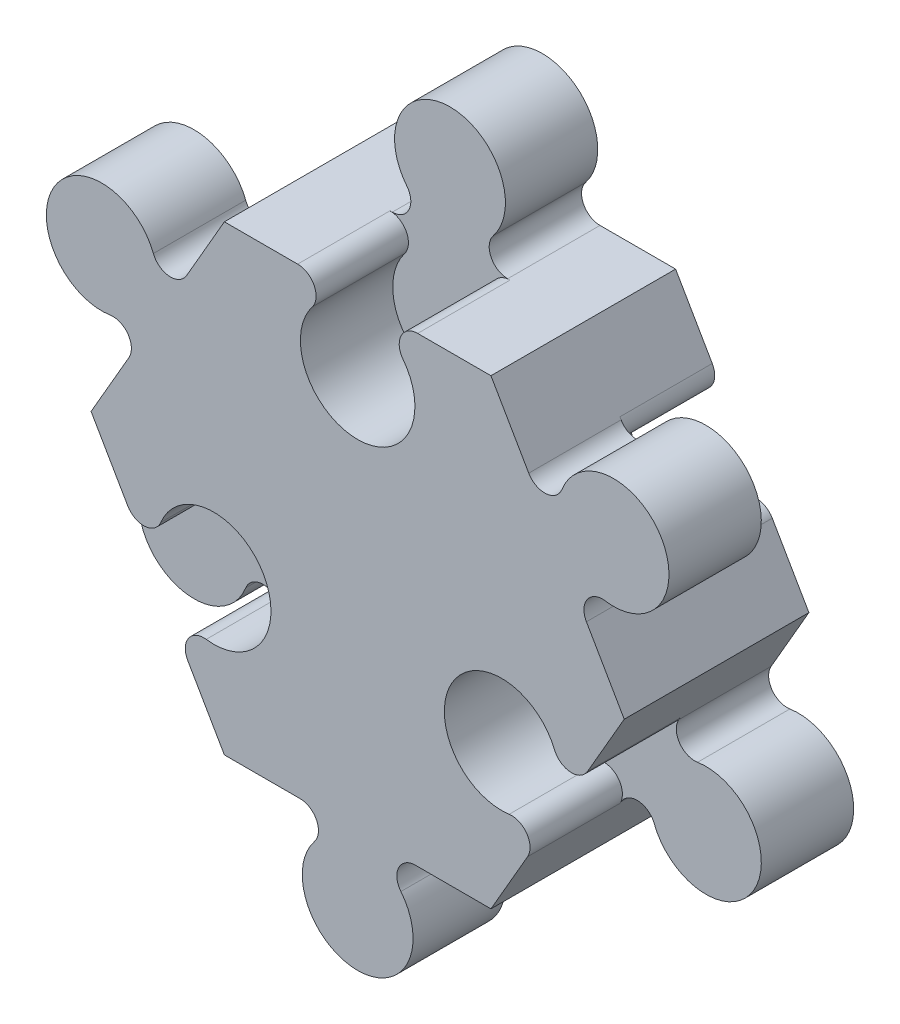
SolidWorks part; units mm, degrees
ref_plane "前视基准面" through (0, 0, 0) normal (0, 0, 1) x (1, 0, 0)
ref_plane "上视基准面" through (0, 0, 0) normal (0, 1, 0) x (1, 0, 0)
ref_plane "右视基准面" through (0, 0, 0) normal (1, 0, 0) x (0, 0, -1)
sketch "草图1" plane through (0, 0, 0) normal (0, 0, 1) x (1, 0, 0)
  line L1 (14.4338, 0) -> (7.2169, 12.5)
  line L2 (7.2169, 12.5) -> (-7.2169, 12.5)
  line L3 (-7.2169, 12.5) -> (-14.4338, 0)
  line L4 (-14.4338, 0) -> (-7.2169, -12.5)
  line L5 (-7.2169, -12.5) -> (7.2169, -12.5)
  line L6 (7.2169, -12.5) -> (14.4338, 0)
  circle A0 centre (0, 0) radius 12.5 construction
  point P1 (0, 0)
  dimension "D1" = 25
extrude "凸台-拉伸1" add sketch "草图1" along normal blind 10
sketch "草图2" plane through (0, 0, 0) normal (0, 0, -1) x (-1, 0, 0)
  line L2 (-7.2169, 12.5) -> (7.2169, 12.5) construction
  line L3 (-3.1225, 12.5) -> (3.1225, 12.5)
  line L4 (0, 19.7238) -> (0, 10.5872) construction
  arc A0 (2.3419, 14.125) -> (-2.3419, 14.125) centre (0, 16) ccw
  arc A1 (2.3419, 14.125) -> (3.1225, 12.5) centre (3.1225, 13.5) ccw
  arc A2 (-2.3419, 14.125) -> (-3.1225, 12.5) centre (-3.1225, 13.5) cw
  point P9 (0, 16.1627)
  dimension "D1" = 6
  dimension "D2" = 2
  dimension "D3" = 3.5
extrude "凸台-拉伸2" add sketch "草图2" against normal blind 5
sketch "草图3" plane through (0, 0, 0) normal (0, 0, -1) x (-1, 0, 0)
  line L0 (-3.1225, -12.5) -> (3.1225, -12.5) construction
  line L1 (7.2169, -12.5) -> (-7.2169, -12.5) construction
  line L2 (-3.2496, -12.5) -> (0, -12.5)
  line L3 (0, 1.3937) -> (0, -16.0678) construction
  line L4 (3.2496, -12.5) -> (-3.2496, -12.5)
  arc A6 (2.3419, -10.875) -> (-2.3419, -10.875) centre (0, -9) ccw construction
  arc A7 (2.3419, -10.875) -> (3.1225, -12.5) centre (3.1225, -11.5) ccw construction
  arc A8 (-2.3419, -10.875) -> (-3.1225, -12.5) centre (-3.1225, -11.5) cw construction
  arc A9 (2.4199, -10.9375) -> (-2.457, -10.8902) centre (0, -9) ccw
  arc A10 (-3.2496, -12.5) -> (-2.457, -10.8902) centre (-3.2496, -11.5) ccw
  arc A11 (2.4199, -10.9375) -> (-2.4199, -10.9375) centre (0, -9) ccw construction
  arc A12 (3.2496, -12.5) -> (2.457, -10.8902) centre (3.2496, -11.5) cw
  dimension "D1" = 1
  dimension "D2" = 3
  dimension "D5" = 1
  dimension "D3" = 3.5
  dimension "D4" = 0.1
extrude "切除-拉伸2" cut sketch "草图3" against normal blind 5 contours A10 A12 A9 region at (0, -9.3315, 0)
ref_axis "基准轴1" through (0, 0, 0) along (0, 0, -1)
pattern_circular "阵列(圆周)1" count 3 over 360 about axis through (0, 0, 0) along (0, 0, -1) of "凸台-拉伸2", "切除-拉伸2"
sketch "草图5" plane through (0, 0, 10) normal (0, 0, 1) x (1, 0, 0)
  line L0 (7.2169, -12.5) -> (9.2005, -9.0642)
  line L1 (3.1225, -12.5) -> (7.2169, -12.5)
  line L2 (-7.2169, -12.5) -> (-3.1225, -12.5)
  line L3 (-9.2005, -9.0642) -> (-7.2169, -12.5)
  line L4 (-14.4338, 0) -> (-12.4501, -3.4358)
  line L5 (-12.3866, 3.5458) -> (-14.4338, 0)
  line L6 (-7.2169, 12.5) -> (-9.2641, 8.9542)
  line L7 (-3.2496, 12.5) -> (-7.2169, 12.5)
  line L8 (7.2169, 12.5) -> (3.2496, 12.5)
  line L9 (9.2641, 8.9542) -> (7.2169, 12.5)
  line L10 (14.4338, 0) -> (12.3866, 3.5458)
  line L11 (12.4501, -3.4358) -> (14.4338, 0)
  arc A0 (10.6597, -3.3173) -> (8.2027, -7.573) centre (7.7942, -4.5) ccw
  arc A1 (9.2005, -9.0642) -> (8.2027, -7.573) centre (8.3345, -8.5642) ccw
  arc A2 (3.1225, -12.5) -> (2.3419, -14.125) centre (3.1225, -13.5) ccw
  arc A3 (-2.3419, -14.125) -> (2.3419, -14.125) centre (0, -16) ccw
  arc A4 (-2.3419, -14.125) -> (-3.1225, -12.5) centre (-3.1225, -13.5) ccw
  arc A5 (-8.2027, -7.573) -> (-9.2005, -9.0642) centre (-8.3345, -8.5642) ccw
  arc A6 (-8.2027, -7.573) -> (-10.6597, -3.3173) centre (-7.7942, -4.5) ccw
  arc A7 (-12.4501, -3.4358) -> (-10.6597, -3.3173) centre (-11.5841, -2.9358) ccw
  arc A8 (-12.3866, 3.5458) -> (-13.4035, 5.0344) centre (-13.2526, 4.0458) ccw
  arc A9 (-11.0617, 9.0906) -> (-13.4035, 5.0344) centre (-13.8564, 8) ccw
  arc A10 (-11.0617, 9.0906) -> (-9.2641, 8.9542) centre (-10.1301, 9.4542) ccw
  arc A11 (-2.457, 10.8902) -> (-3.2496, 12.5) centre (-3.2496, 11.5) ccw
  arc A12 (-2.457, 10.8902) -> (2.457, 10.8902) centre (0, 9) ccw
  arc A13 (3.2496, 12.5) -> (2.457, 10.8902) centre (3.2496, 11.5) ccw
  arc A14 (9.2641, 8.9542) -> (11.0617, 9.0906) centre (10.1301, 9.4542) ccw
  arc A15 (13.4035, 5.0344) -> (11.0617, 9.0906) centre (13.8564, 8) ccw
  arc A16 (13.4035, 5.0344) -> (12.3866, 3.5458) centre (13.2526, 4.0458) ccw
  arc A17 (10.6597, -3.3173) -> (12.4501, -3.4358) centre (11.5841, -2.9358) ccw
  point P0 (0, 0)
extrude "凸台-拉伸3" add sketch "草图5" against normal blind 5
sketch "草图6" plane through (0, 0, 10) normal (0, 0, 1) x (1, 0, 0)
  line L0 (7.2169, -12.5) -> (9.2005, -9.0642)
  line L1 (3.1225, -12.5) -> (7.2169, -12.5)
  line L2 (-7.2169, -12.5) -> (-3.1225, -12.5)
  line L3 (-9.2005, -9.0642) -> (-7.2169, -12.5)
  line L4 (-14.4338, 0) -> (-12.4501, -3.4358)
  line L5 (-12.3866, 3.5458) -> (-14.4338, 0)
  line L6 (-7.2169, 12.5) -> (-9.2641, 8.9542)
  line L7 (-3.2496, 12.5) -> (-7.2169, 12.5)
  line L8 (7.2169, 12.5) -> (3.2496, 12.5)
  line L9 (9.2641, 8.9542) -> (7.2169, 12.5)
  line L10 (14.4338, 0) -> (12.3866, 3.5458)
  line L11 (12.4501, -3.4358) -> (14.4338, 0)
  line L13 (26.1796, 0.365) -> (12.7737, 22.8547)
  line L14 (12.7737, 22.8547) -> (-13.4059, 22.4897)
  line L15 (-13.4059, 22.4897) -> (-26.1796, -0.365)
  line L16 (-26.1796, -0.365) -> (-12.7737, -22.8547)
  line L17 (-12.7737, -22.8547) -> (13.4059, -22.4897)
  line L18 (13.4059, -22.4897) -> (26.1796, 0.365)
  arc A0 (10.6597, -3.3173) -> (8.2027, -7.573) centre (7.7942, -4.5) ccw
  arc A1 (9.2005, -9.0642) -> (8.2027, -7.573) centre (8.3345, -8.5642) ccw
  arc A2 (3.1225, -12.5) -> (2.3419, -14.125) centre (3.1225, -13.5) ccw
  arc A3 (-2.3419, -14.125) -> (2.3419, -14.125) centre (0, -16) ccw
  arc A4 (-2.3419, -14.125) -> (-3.1225, -12.5) centre (-3.1225, -13.5) ccw
  arc A5 (-8.2027, -7.573) -> (-9.2005, -9.0642) centre (-8.3345, -8.5642) ccw
  arc A6 (-8.2027, -7.573) -> (-10.6597, -3.3173) centre (-7.7942, -4.5) ccw
  arc A7 (-12.4501, -3.4358) -> (-10.6597, -3.3173) centre (-11.5841, -2.9358) ccw
  arc A8 (-12.3866, 3.5458) -> (-13.4035, 5.0344) centre (-13.2526, 4.0458) ccw
  arc A9 (-11.0617, 9.0906) -> (-13.4035, 5.0344) centre (-13.8564, 8) ccw
  arc A10 (-11.0617, 9.0906) -> (-9.2641, 8.9542) centre (-10.1301, 9.4542) ccw
  arc A11 (-2.457, 10.8902) -> (-3.2496, 12.5) centre (-3.2496, 11.5) ccw
  arc A12 (-2.457, 10.8902) -> (2.457, 10.8902) centre (0, 9) ccw
  arc A13 (3.2496, 12.5) -> (2.457, 10.8902) centre (3.2496, 11.5) ccw
  arc A14 (9.2641, 8.9542) -> (11.0617, 9.0906) centre (10.1301, 9.4542) ccw
  arc A15 (13.4035, 5.0344) -> (11.0617, 9.0906) centre (13.8564, 8) ccw
  arc A16 (13.4035, 5.0344) -> (12.3866, 3.5458) centre (13.2526, 4.0458) ccw
  arc A17 (10.6597, -3.3173) -> (12.4501, -3.4358) centre (11.5841, -2.9358) ccw
  circle A18 centre (0, 0) radius 22.6744 construction
  point P0 (0, 0)
extrude "切除-拉伸3" cut sketch "草图6" against normal blind 5
